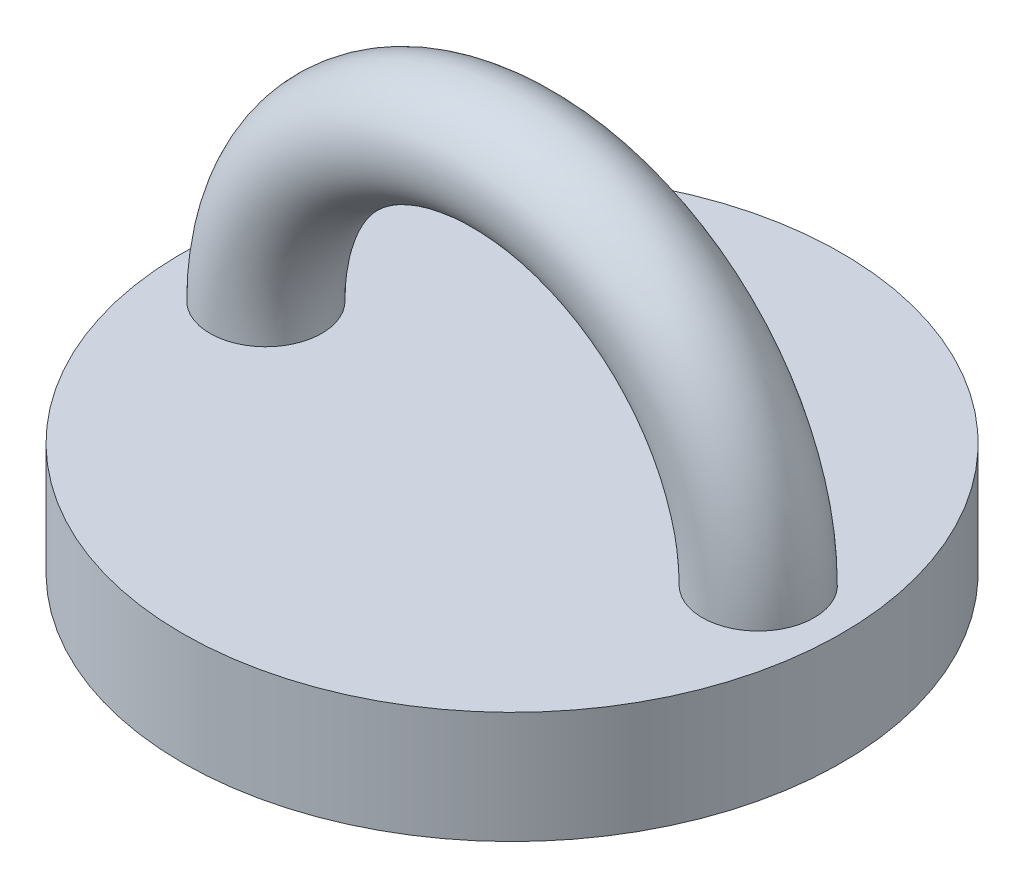
SolidWorks part; units mm, degrees
material "PP Homopolymer"
ref_plane "Front Plane" through (0, 0, 0) normal (0, 0, 1) x (1, 0, 0)
ref_plane "Top Plane" through (0, 0, 0) normal (0, 1, 0) x (1, 0, 0)
ref_plane "Right Plane" through (0, 0, 0) normal (1, 0, 0) x (0, 0, -1)
sketch "Sketch1" plane through (0, 0, 0) normal (0, 1, 0) x (1, 0, 0)
  circle A0 centre (0, 0) radius 29.45
  dimension "D1" = 58.9
extrude "Boss-Extrude1" add sketch "Sketch1" along normal blind 10
sketch "Sketch2" plane through (0, 10, 0) normal (0, 1, 0) x (1, 0, 0)
  line L0 (0, -39.386) -> (0, 43.8596) construction
  circle A1 centre (-22, 0) radius 5
  dimension "D2" = 10
  dimension "D4" = 22
revolve "Revolve3" add sketch "Sketch2" angle 180 about L0
